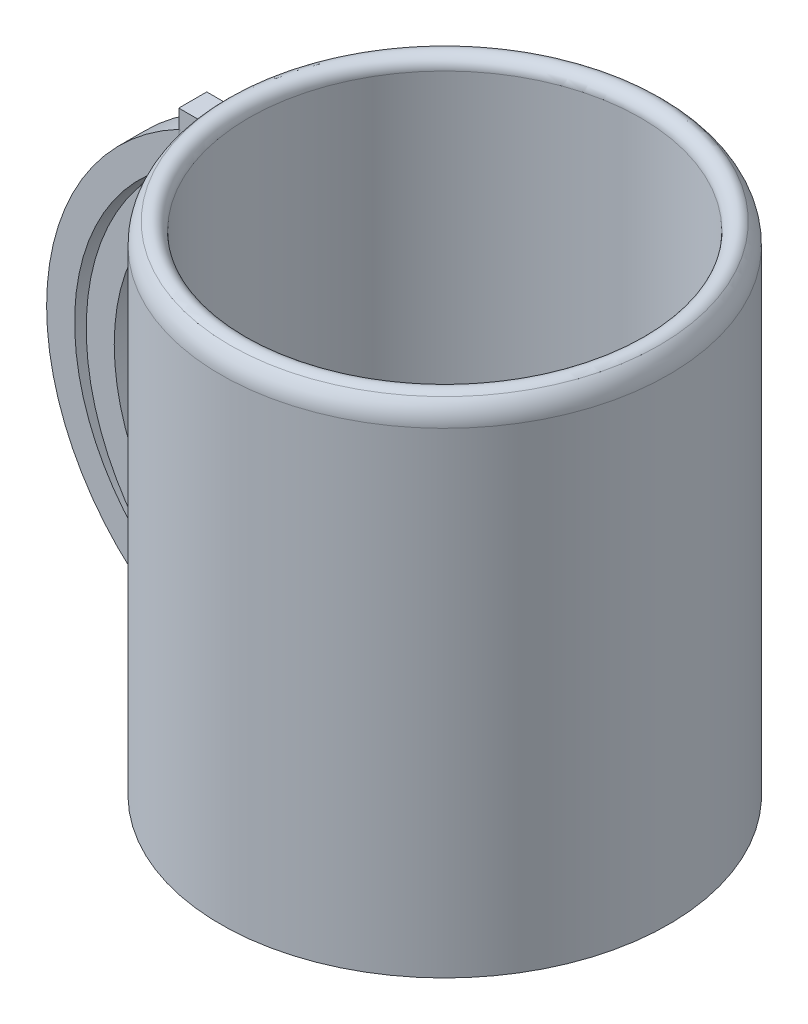
SolidWorks part; units mm, degrees
other "Apoio"
other "Caneca_Corpo"
other "Alça_02"
other "Alça_01"
ref_plane "Plano frontal" through (0, 0, 0) normal (0, 0, 1) x (1, 0, 0)
ref_plane "Plano superior" through (0, 0, 0) normal (0, 1, 0) x (1, 0, 0)
ref_plane "Plano direito" through (0, 0, 0) normal (1, 0, 0) x (0, 0, -1)
sketch "Esboço3" plane through (0, 0, 0) normal (0, 0, 1) x (1, 0, 0)
  line L0 (0, 0) -> (0, 90) construction
  line L1 (0, 0) -> (-40, 0)
  line L3 (-40, 90) -> (0, 90)
  line L5 (-40, 90) -> (-40, 0)
  line L6 (0, 90) -> (0, 0)
  dimension "D1" = 90
  dimension "D5" = 40
revolve "Revolução3" add sketch "Esboço3" angle 360 about L0
sketch "Esboço9" plane through (0, 90, 0) normal (0, 1, 0) x (1, 0, 0)
  circle A0 centre (0, 0) radius 35
  dimension "D1" = 70
extrude "Corte-extrusão2" cut sketch "Esboço9" against normal blind 80
fillet "Filete5" radius 5 2 edges at (0, 90, -40) (0, 90, 35) type face fillet first side face at (0, 90, 35) second side face at (0, 0, -40) second side face at (0, 10, 35)
fillet "Filete7" radius 2 1 edges at (0, 90, 35) type face fillet first side face at (0, 90, 35) second side face at (0, 10, 35)
sketch "Esboço10" plane through (0, 0, 0) normal (0, 0, 1) x (1, 0, 0)
  line L2 (-40, 85) -> (-40, 0)
  line L3 (40, 85) -> (-40, 85) construction
  line L4 (-40, 85) -> (-40, 0) construction
  arc A0 (-40, 73.5775) -> (-40, 11.7943) centre (-19.3819, 42.6859) ccw
  arc A1 (-40, 78.5775) -> (-40, 6.6368) centre (-24.3813, 42.6072) ccw
  point P12 (-56.5221, 42.6859)
  point P14 (-63.5962, 42.6072)
  dimension "D1" = 5
  dimension "D2" = 5
  dimension "D3" = 7.0745
extrude "Extrusão-Fina2" add sketch "Esboço10" along normal mid plane 5 separate body thin thin type one direction wall 5
